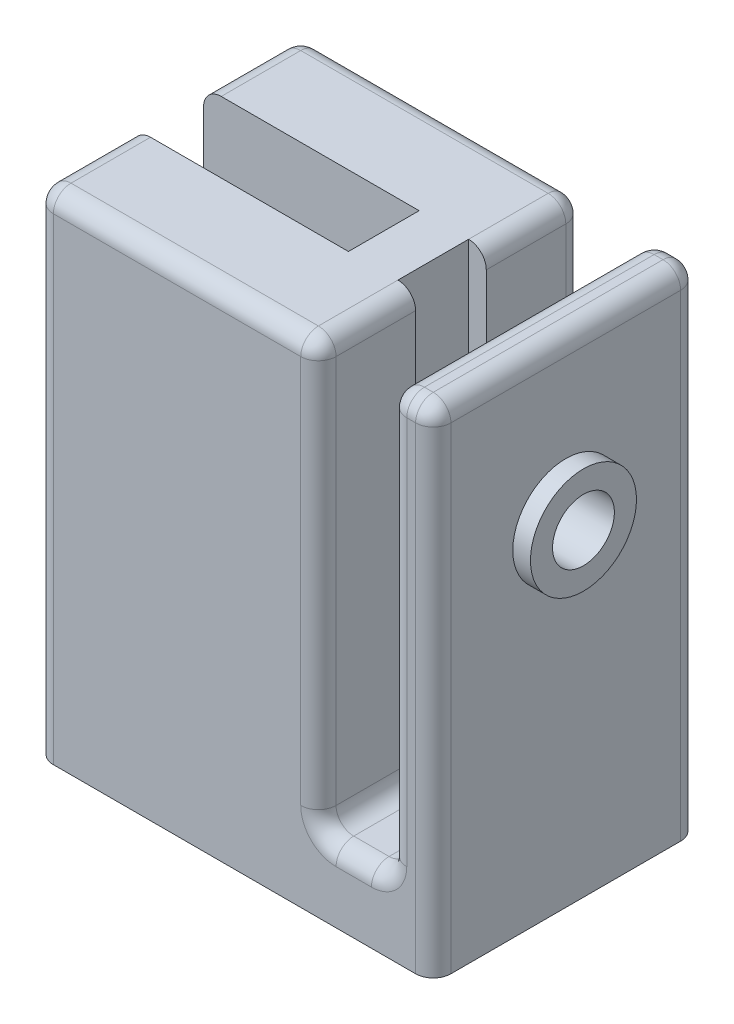
SolidWorks part; units mm, degrees
ref_plane "Plan de face" through (0, 0, 0) normal (0, 0, 1) x (1, 0, 0)
ref_plane "Plan de dessus" through (0, 0, 0) normal (0, 1, 0) x (1, 0, 0)
ref_plane "Plan de droite" through (0, 0, 0) normal (1, 0, 0) x (0, 0, -1)
sketch "Esquisse1" plane through (0, 0, 0) normal (0, 1, 0) x (1, 0, 0)
  line L0 (0, 0) -> (0, 15) construction
  line L1 (0, 0) -> (57, 0) construction
  line L2 (6, 15) -> (6, -15) construction
  line L3 (-16.5, -15) -> (28.5, -15)
  line L4 (-16.5, -15) -> (-16.5, 15)
  line L5 (-16.5, 15) -> (28.5, 15)
  line L6 (28.5, -15) -> (28.5, 15)
  point P8 (28.5, 0)
  dimension "D1" = 30
  dimension "D2" = 45
  dimension "D3" = 6
extrude "Boss.-Extru.1" add sketch "Esquisse1" along normal blind 8
sketch "Esquisse5" plane through (-16.5, 0, 0) normal (-1, 0, 0) x (0, 0, 1)
  line L0 (-15, 8) -> (-15, 56)
  line L1 (-15, 56) -> (15, 56)
  line L2 (15, 56) -> (15, 8)
  line L3 (-15, 8) -> (15, 8)
  dimension "D1" = 48
extrude "Boss.-Extru.3" add sketch "Esquisse5" against normal blind 32
sketch "Esquisse6" plane through (-16.5, 0, 0) normal (-1, 0, 0) x (0, 0, 1)
  line L0 (15, 8) -> (-15, 8) construction
  line L1 (15, 8) -> (-15, 8) construction
  line L2 (10.25, 48) -> (4, 48)
  line L3 (-10.25, 48) -> (-10.25, 8)
  line L4 (-10.25, 8) -> (10.25, 8)
  line L5 (10.25, 8) -> (10.25, 48)
  line L6 (0, 0) -> (0, 56) construction
  line L7 (-15, 0) -> (15, 0) construction
  line L8 (15, 56) -> (-15, 56) construction
  line L9 (-15, 28) -> (15, 28) construction
  line L10 (-15, 56) -> (-15, 0) construction
  line L11 (15, 56) -> (15, 0) construction
  line L12 (4, 48) -> (4, 56)
  line L13 (4, 56) -> (-4, 56)
  line L14 (-4, 56) -> (-4, 48)
  line L15 (-4, 48) -> (-10.25, 48)
  point P11 (0, 8)
  point P20 (0, 28)
  point P25 (0, 56)
  dimension "D1" = 20.5
  dimension "D2" = 8
  dimension "D3" = 40
extrude "Enlèv. mat.-Extru.1" cut sketch "Esquisse6" against normal blind 27 contours L2 L12 L13 L14 L15 L3 L4 L5
sketch "Esquisse7" plane through (-16.5, 0, 0) normal (-1, 0, 0) x (0, 0, 1)
  line L0 (0, 0) -> (0, 8) construction
  line L1 (-15, 0) -> (15, 0) construction
  line L2 (-10.25, 8) -> (10.25, 8) construction
  line L3 (-5, 4) -> (5, 4) construction
  circle A0 centre (-5, 4) radius 1.3509
  circle A1 centre (5, 4) radius 1.3509
  dimension "D1" = 10
  dimension "D2" = 4
sketch "Esquisse14" plane through (0, 56, 0) normal (0, 1, 0) x (1, 0, 0)
  line L1 (13.5, 4) -> (19.5, 4)
  line L3 (15.5, -15) -> (15.5, 15) construction
  line L4 (19.5, 4) -> (19.5, -4)
  line L5 (10.5, -4) -> (-16.5, -4) construction
  line L6 (15.5, -4) -> (13.5, -4) construction
  line L7 (15.5, -4) -> (15.5, 4) construction
  line L8 (15.5, 4) -> (13.5, 4) construction
  line L9 (13.5, -4) -> (13.5, 4)
  line L10 (10.5, 4) -> (-16.5, 4) construction
  line L11 (19.5, -4) -> (13.5, -4)
  dimension "D1" = 2
  dimension "D2" = 6
extrude "Enlèv. mat.-Extru.2" cut sketch "Esquisse14" against normal through all
hole_wizard "Dégagement M31" positions "Esquisse12" profile "Esquisse13" hole size "M3" standard "ISO"
sketch "Esquisse12" plane through (-16.5, 0, 0) normal (-1, 0, 0) x (0, 0, 1)
  point P0 (5, 4)
  point P3 (-5, 4)
sketch "Esquisse13" plane through (-16.5, 4, 5) normal (0, 1, 0) x (0, 0, 1)
  line L0 (0, 0) -> (0, 7.9614)
  line L1 (0, 7.9614) -> (1.6, 7)
  line L2 (1.6, 7) -> (1.6, 0)
  line L5 (1.6, 0) -> (0, 0)
  line L10 (0, 7.9614) -> (-1.6, 7) construction
  line L11 (0, -6.35) -> (0, 107.95) construction
  dimension "Diamètre du perçage" = 3.2
  dimension "Profondeur du perçage" = 7
  dimension "Angle de pointe" = 118
sketch "Esquisse16" plane through (28.5, 0, 0) normal (1, 0, 0) x (0, 0, -1)
  line L0 (0, 0) -> (0, 56) construction
  line L1 (-15, 0) -> (15, 0) construction
  line L2 (4, 56) -> (-4, 56) construction
  line L3 (-15, 8) -> (15, 8) construction
  line L4 (-15, 8) -> (-15, 56) construction
  line L5 (15, 56) -> (15, 8) construction
  line L6 (-15, 56) -> (-4, 56) construction
  line L7 (-15, 8) -> (15, 8)
  line L8 (-15, 8) -> (-15, 56)
  line L9 (15, 56) -> (15, 8)
  line L10 (-15, 56) -> (15, 56)
  circle A0 centre (0, 38) radius 3.5
  dimension "D1" = 7
  dimension "D2" = 18
extrude "Boss.-Extru.4" add sketch "Esquisse16" against normal blind 5
fillet "Congé1" radius 2 23 edges at (19.5, 8, -15) (19.5, 8, 15) (28.5, 28, 15) (28.5, 28, -15) (-16.5, 28, 15) (-16.5, 28, -15) (-16.5, 56, -9.5) (-16.5, 56, 9.5) (15.5, 8, -9.5) (15.5, 8, 9.5) (-0.5, 56, -15) (15.5, 32, -15) (-0.5, 56, 15) (15.5, 32, 15) (15.5, 56, -9.5) (15.5, 56, 9.5) (26, 56, 15) (23.5, 56, 0) (26, 56, -15) (28.5, 56, 0) (23.5, 8, 0) (23.5, 32, -15) (23.5, 32, 15)
sketch "Esquisse17" plane through (23.5, 0, 0) normal (-1, 0, 0) x (0, 0, 1)
  line L0 (0, 0) -> (0, 56) construction
  line L1 (-13, 56) -> (13, 56) construction
  line L3 (-5, 33) -> (5, 33)
  line L4 (-5, 33) -> (-5, 43)
  line L5 (-5, 43) -> (5, 43)
  line L6 (5, 33) -> (5, 43)
  line L7 (-5, 33) -> (5, 43) construction
  line L8 (-5, 43) -> (5, 33) construction
  circle A0 centre (0, 38) radius 3.5 construction
  circle A1 centre (0, 38) radius 3.5 construction
  dimension "D1" = 10
extrude "Enlèv. mat.-Extru.3" cut sketch "Esquisse17" against normal blind 2
sketch "Esquisse18" plane through (28.5, 0, 0) normal (1, 0, 0) x (0, 0, -1)
  line L0 (0, 0) -> (0, 54) construction
  line L1 (-13, 0) -> (13, 0) construction
  line L2 (13, 54) -> (-13, 54) construction
  circle A0 centre (0, 38) radius 3.5 construction
  circle A1 centre (0, 38) radius 3.5
  circle A2 centre (0, 38) radius 6
  dimension "D1" = 12
extrude "Boss.-Extru.5" add sketch "Esquisse18" along normal blind 2
ref_axis "Axe2" through (0, 58.8, 0) along (0, -1, 0)
sketch "Esquisse21" plane through (0, 8, 0) normal (0, 1, 0) x (1, 0, 0)
  line L0 (0, 0) -> (0, 23.8533) construction
  line L1 (-7.5, 0) -> (7.5, 0) construction
  point P6 (0, 0)
  dimension "D1" = 15
hole_wizard "Fraisage pour vis à tête fraisée M31" positions "Esquisse22" profile "Esquisse23" countersink size "M3" standard "ISO" end condition through all
sketch "Esquisse22" plane through (0, 8, 0) normal (0, 1, 0) x (1, 0, 0)
  point P0 (-7.5, 0)
  point P3 (7.5, 0)
sketch "Esquisse23" plane through (-7.5, 8, 0) normal (1, 0, 0) x (0, 0, 1)
  line L0 (0, 0) -> (0, 8)
  line L1 (0, 8) -> (1.7, 8)
  line L2 (1.7, 8) -> (1.7, 1.45)
  line L3 (1.7, 1.45) -> (3.15, 0)
  line L5 (3.15, 0) -> (0, 0)
  line L6 (-1.7, 1.45) -> (-3.15, 0) construction
  line L11 (0, -6.35) -> (0, 107.95) construction
  dimension "Diamètre du perçage jusqu'au prochain" = 3.4
  dimension "Profondeur du perçage jusqu'au prochain" = 8
  dimension "Diamètre du fraisage entrant" = 6.3
  dimension "Angle du fraisage entrant" = 90
sketch "Esquisse24" plane through (10.5, 0, 0) normal (-1, 0, 0) x (0, 0, 1)
  line L0 (0, 0) -> (0, 79.3544) construction
  line L1 (4, 56) -> (-4, 56) construction
  line L2 (-4, 56) -> (-4, 48) construction
  line L3 (4, 48) -> (4, 56) construction
  line L4 (4, 56) -> (-4, 56)
  line L5 (-4, 56) -> (-4, 48)
  line L6 (4, 48) -> (4, 56)
  line L7 (4, 48) -> (-4, 48)
extrude "Boss.-Extru.6" add sketch "Esquisse24" along normal blind 2.6
ref_axis "Axe3" through (-83.577, 38, 0) along (1, 0, 0)
